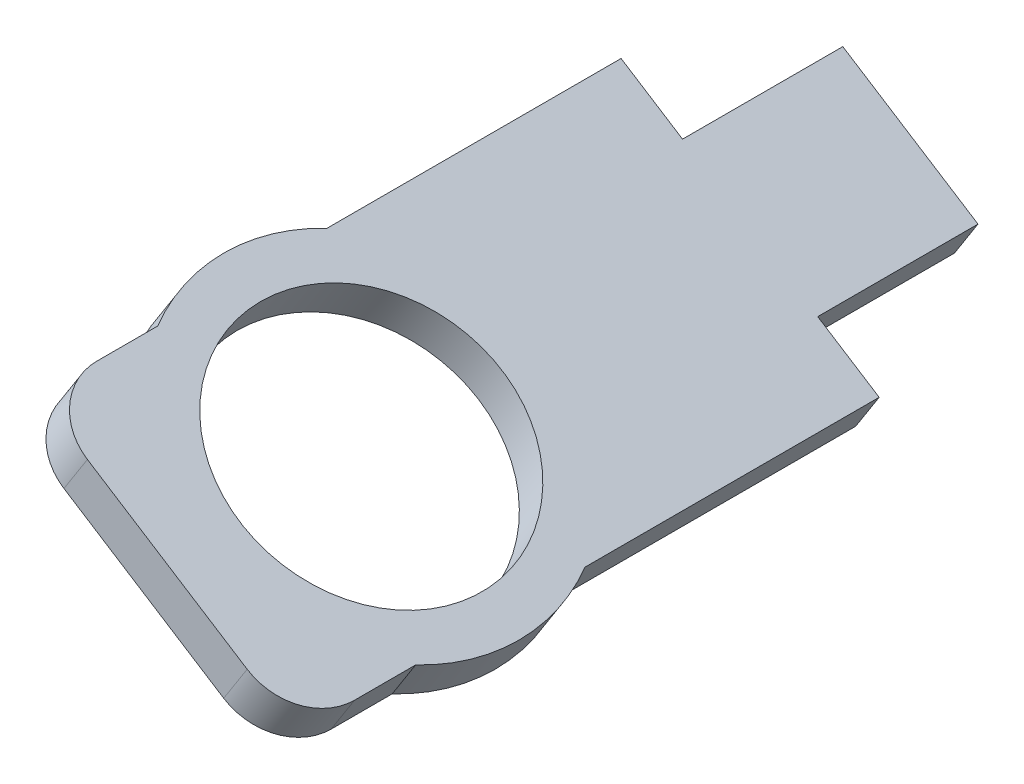
SolidWorks part; units mm, degrees
ref_plane "Alzado" through (0, 0, 0) normal (0, 0, 1) x (1, 0, 0)
ref_plane "Planta" through (0, 0, 0) normal (0, 1, 0) x (1, 0, 0)
ref_plane "Vista lateral" through (0, 0, 0) normal (1, 0, 0) x (0, 0, -1)
sketch "Croquis1" plane through (0, 0, 0) normal (0, 0, 1) x (1, 0, 0)
  line L77 (-32.0432, 26.1671) -> (-30.4313, 28.6973)
  line L78 (-41.3205, 32.0774) -> (-32.0432, 26.1671)
  line L79 (-39.7086, 34.6076) -> (-41.3205, 32.0774)
  line L80 (-30.4313, 28.6973) -> (-39.7086, 34.6076)
  line L81 (-32.0432, 26.1671) -> (-30.4313, 28.6973)
  line L82 (-41.3205, 32.0774) -> (-32.0432, 26.1671)
  line L83 (-39.7086, 34.6076) -> (-41.3205, 32.0774)
  line L84 (-30.4313, 28.6973) -> (-39.7086, 34.6076)
  dimension "D1" = 0
extrude "Saliente-Extruir1" add sketch "Croquis1" against normal up to surface (11 mm away)
sketch "Croquis2" plane through (0, 0, 0) normal (0, 0, 1) x (1, 0, 0)
  line L4 (-26.2143, 26.0108) -> (-43.9255, 37.2941)
  line L5 (-32.0432, 26.1671) -> (-27.8262, 23.4806)
  line L6 (-32.0432, 26.1671) -> (-45.5374, 34.7639)
  line L8 (-23.5278, 30.2277) -> (-41.239, 41.511)
  line L9 (-41.239, 41.511) -> (-48.2239, 30.5469)
  line L10 (-48.2239, 30.5469) -> (-30.5127, 19.2637)
  line L11 (-30.5127, 19.2637) -> (-23.5278, 30.2277)
  line L13 (-43.9255, 37.2941) -> (-45.5374, 34.7639)
  line L15 (-27.8262, 23.4806) -> (-26.2143, 26.0108)
  dimension "D1" = 5
extrude "Saliente-Extruir2" add sketch "Croquis2" along normal blind 40
sketch "Croquis3" plane through (4.2191, 6.6226, 0) normal (0.5373, 0.8434, 0) x (0.8434, -0.5373, 0)
  circle A0 centre (-46.5845, -26) radius 9
  circle A1 centre (-46.5845, -26) radius 12
extrude "Saliente-Extruir3" add sketch "Croquis3" against normal up to surface (3 mm away) up to face at (-36.6818, 29.1223, 7.25)
extrude "Cortar-Extruir1" cut sketch "Croquis3<2>" against normal blind 10 contours A0 region at (-35.0699, 31.6524, 26)
sketch "Croquis3<2>" plane through (4.2191, 6.6226, 0) normal (0.5373, 0.8434, 0) x (0.8434, -0.5373, 0) same geometry as "Croquis3"
fillet "Redondeo1" radius 4 2 edges at (-44.7315, 36.029, 40) (-27.0203, 24.7457, 40)
